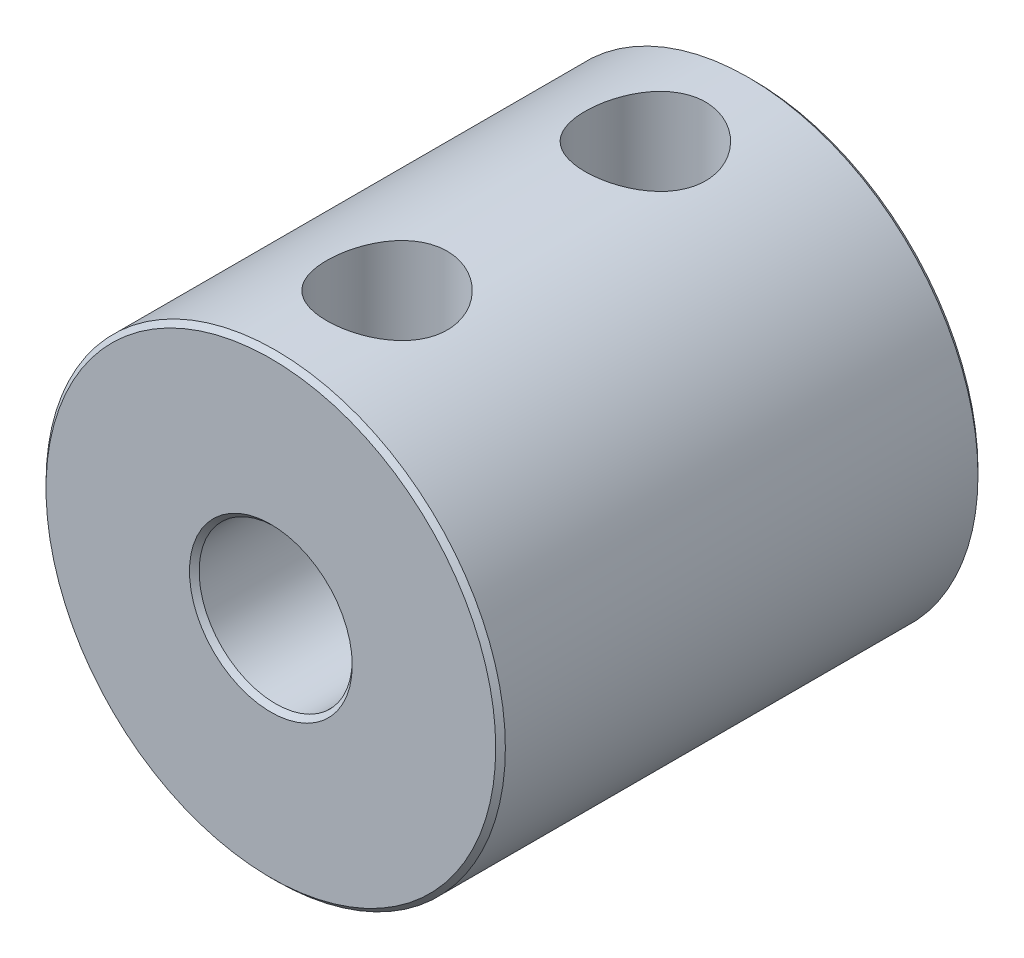
SolidWorks part; units mm, degrees
ref_plane "Front Plane" through (0, 0, 0) normal (0, 0, 1) x (1, 0, 0)
ref_plane "Top Plane" through (0, 0, 0) normal (0, 1, 0) x (1, 0, 0)
ref_plane "Right Plane" through (0, 0, 0) normal (1, 0, 0) x (0, 0, -1)
sketch "Sketch1" plane through (0, 0, 0) normal (0, 0, 1) x (1, 0, 0)
  circle A0 centre (0, 0) radius 4.7625
  circle A1 centre (0, 0) radius 1.5875
  circle A2 centre (0, 0) radius 2
  dimension "D1" = 3.175
  dimension "D2" = 4
  dimension "D3" = 9.525
extrude "Boss-Extrude1" add sketch "Sketch1" along normal blind 5 contours A0 | A1
extrude "Boss-Extrude2" add sketch "Sketch1<3>" against normal blind 5 contours A0 | A2
sketch "Sketch1<3>" plane through (0, 0, 0) normal (0, 0, 1) x (1, 0, 0) same geometry as "Sketch1"
hole_wizard "M3x0.5 Tapped Hole1" positions "Sketch2" profile "Sketch3" tap size "M3x0.5" standard "ANSI Metric" end condition through all
sketch "Sketch2" plane through (0, 0, 0) normal (0, 1, 0) x (1, 0, 0)
  point P0 (0, -2.5915)
  point P2 (0, 2.7648)
  dimension "D1" = 2.5915
  dimension "D2" = 2.7648
sketch "Sketch3" plane through (0, 0, 2.5915) normal (1, 0, 0) x (0, 0, -1)
  line L0 (0, 0) -> (0, 4.7625)
  line L1 (0, 4.7625) -> (1.25, 4.7625)
  line L2 (1.25, 4.7625) -> (1.25, 0)
  line L5 (1.25, 0) -> (0, 0)
  line L11 (0, -6.35) -> (0, 107.95) construction
  dimension "Thru Tap Drill Dia." = 2.5
  dimension "Thru Tap Drill Depth" = 4.7625
cosmetic thread "Hole Thread1" parameters "D2"=3
cosmetic thread "Hole Thread2" parameters "D2"=3
chamfer "Chamfer1" distance 0.1 angle 45 4 edges at (4.7625, 0, -5) (2, 0, -5) (1.5875, 0, 5) (4.7625, 0, 5)
